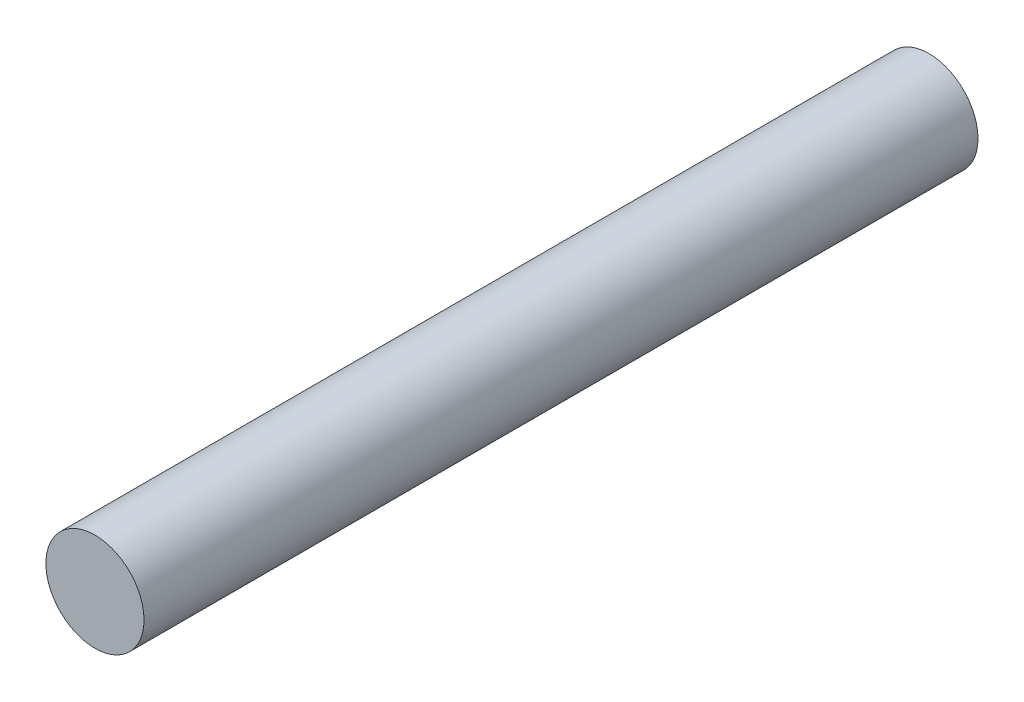
SolidWorks part; units mm, degrees
material "Hexcel AS4C (3000 Filaments)"
ref_plane "Front" through (0, 0, 0) normal (0, 0, 1) x (1, 0, 0)
ref_plane "Top" through (0, 0, 0) normal (0, 1, 0) x (1, 0, 0)
ref_plane "Right" through (0, 0, 0) normal (1, 0, 0) x (0, 0, -1)
sketch "Sketch1" plane through (0, 0, 0) normal (0, 0, 1) x (1, 0, 0)
  circle A0 centre (0, 0) radius 3.175
  dimension "D1" = 6.35
extrude "Boss-Extrude1" add sketch "Sketch1" along normal blind 53.975
equation "\"truss_member_od\" = .25in"
equation "\"truss_member_L1\" = 2.125in"
equation "\"connector_hole_depth\" = .375in"
equation "\"truss_member_L2\" = 2.875in"
equation "\"D1@Boss-Extrude1\"=\"truss_member_L1\""
equation "\"D1@Sketch1\"=\"truss_member_od\""
